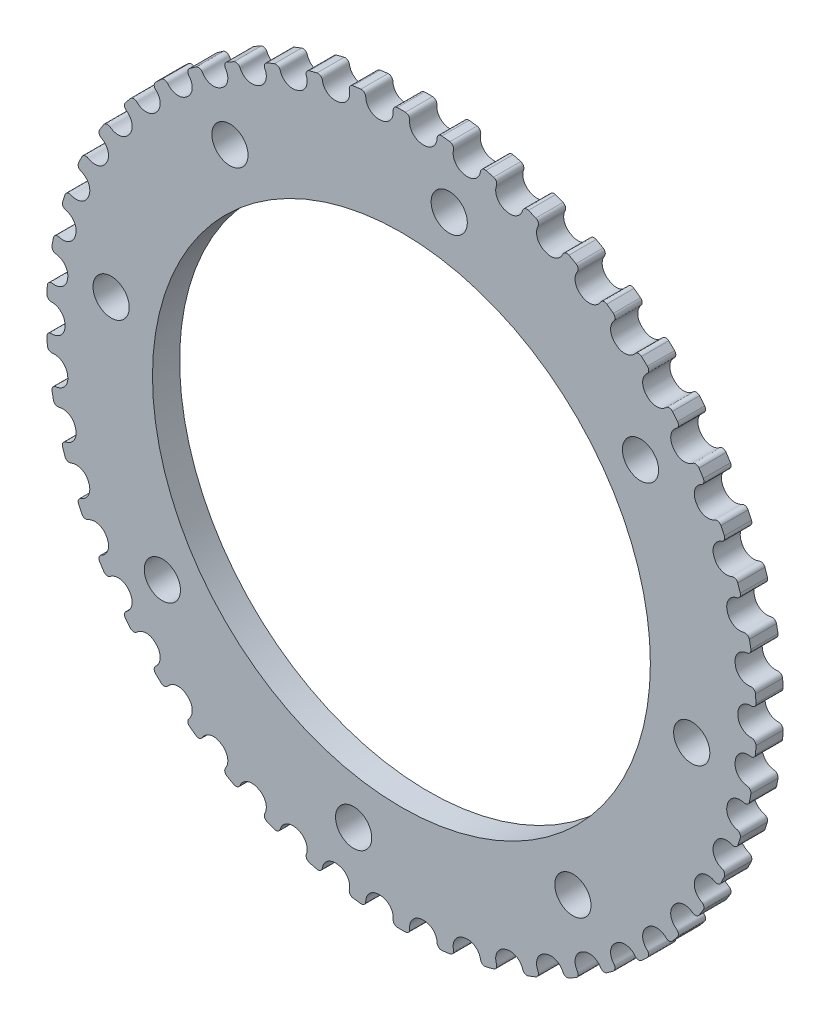
SolidWorks part; units mm, degrees
material "Thornel Mat VMA"
ref_plane "Front Plane" through (0, 0, 0) normal (0, 0, 1) x (1, 0, 0)
ref_plane "Top Plane" through (0, 0, 0) normal (0, 1, 0) x (1, 0, 0)
ref_plane "Right Plane" through (0, 0, 0) normal (1, 0, 0) x (0, 0, -1)
ref_axis "Axis1" through (0, 0, 55) along (0, 0, -1)
sketch "SketchRevolveGearBelt01" plane through (0, 0, 0) normal (1, 0, 0) x (0, 0, -1)
  line L0 (0, 0) -> (1, 0) construction
  line L1 (1.5, 0) -> (1.5, 39.2172)
  line L2 (1.5, 39.2172) -> (-1.5, 39.2172)
  line L3 (-1.5, 39.2172) -> (-1.5, 0)
  line L4 (-1.5, 0) -> (1.5, 0)
  dimension "GearBeltSide1" = 1.5
  dimension "GearBeltOutsideDiameter" = 39.2172
  dimension "GearBeltSide2" = 1.5
revolve "GearBelt01" add sketch "SketchRevolveGearBelt01" angle 360 about L0
sketch "SketchToothGearBelt01" plane through (0, 0, 0) normal (0, 0, 1) x (1, 0, 0)
  arc A0 (39.1647, 2.0323) -> (39.1647, -2.0323) centre (0, 0) cw
  spline S0 degree 3 poles (39.1647, -2.0323) (39.166, -2.006) (39.1649, -1.9663) (39.1569, -1.9141) (39.1478, -1.8755) (39.1356, -1.8378) (39.1204, -1.8013) (39.1023, -1.7661) (39.0814, -1.7324) (39.0578, -1.7006) (39.0317, -1.6708) (39.0033, -1.6432) (38.9728, -1.618) (38.9403, -1.5953) (38.9061, -1.5754) (38.8703, -1.5582) (38.8333, -1.5441) (38.7953, -1.533) (38.7565, -1.525) (38.7172, -1.5201) (38.6658, -1.5185) (38.59, -1.5198) (38.4897, -1.516) (38.3775, -1.5026) (38.2667, -1.4805) (38.158, -1.4498) (38.052, -1.4107) (37.9494, -1.3633) (37.8509, -1.3081) (37.7569, -1.2453) (37.6682, -1.1753) (37.5853, -1.0986) (37.5086, -1.0156) (37.4387, -0.9268) (37.376, -0.8329) (37.3208, -0.7343) (37.2735, -0.6317) (37.2344, -0.5257) (37.2037, -0.4169) (37.1817, -0.3061) (37.1683, -0.1939) (37.1652, -0.1051) (37.1655, -0.0405) (37.1655, 0) (37.1655, 0.0405) (37.1652, 0.1051) (37.1683, 0.1939) (37.1817, 0.3061) (37.2037, 0.4169) (37.2344, 0.5257) (37.2735, 0.6317) (37.3208, 0.7343) (37.376, 0.8329) (37.4387, 0.9268) (37.5086, 1.0156) (37.5853, 1.0986) (37.6682, 1.1753) (37.7569, 1.2453) (37.8509, 1.3081) (37.9494, 1.3633) (38.052, 1.4107) (38.158, 1.4498) (38.2667, 1.4805) (38.3775, 1.5026) (38.4897, 1.516) (38.59, 1.5198) (38.6658, 1.5185) (38.7172, 1.5201) (38.7565, 1.525) (38.7953, 1.533) (38.8333, 1.5441) (38.8703, 1.5582) (38.9061, 1.5754) (38.9403, 1.5953) (38.9728, 1.618) (39.0033, 1.6432) (39.0317, 1.6708) (39.0578, 1.7006) (39.0814, 1.7324) (39.1023, 1.7661) (39.1204, 1.8013) (39.1356, 1.8378) (39.1478, 1.8755) (39.1569, 1.9141) (39.1649, 1.9663) (39.166, 2.006) (39.1647, 2.0323) knots 0 0 0 0 0.012346 0.01852 0.024693 0.030866 0.037039 0.043212 0.049386 0.055559 0.061732 0.067905 0.074078 0.080252 0.086425 0.092598 0.098771 0.104944 0.111118 0.117291 0.123464 0.135171 0.152781 0.17039 0.188 0.205609 0.223219 0.240828 0.258438 0.276048 0.293657 0.311267 0.328876 0.346486 0.364095 0.381705 0.399315 0.416924 0.434534 0.452143 0.469753 0.487362 0.493681 0.5 0.506319 0.512638 0.530247 0.547857 0.565466 0.583076 0.600685 0.618295 0.635905 0.653514 0.671124 0.688733 0.706343 0.723952 0.741562 0.759172 0.776781 0.794391 0.812 0.82961 0.847219 0.864829 0.876536 0.882709 0.888882 0.895056 0.901229 0.907402 0.913575 0.919748 0.925922 0.932095 0.938268 0.944441 0.950614 0.956788 0.962961 0.969134 0.975307 0.98148 0.987654 1 1 1 1
extrude "ToothExtrudeCutGearBelt01" cut sketch "SketchToothGearBelt01" against normal blind 7.239 and the other way blind 7.239
pattern_circular "PatternGearBelt01" count 50 every 7.2 about axis through (0, 0, 55) along (0, 0, -1) of "ToothExtrudeCutGearBelt01"
sketch "BoreRevolveSketch" plane through (0, 0, 0) normal (1, 0, 0) x (0, 0, -1)
  line L0 (0, 0) -> (1, 0) construction
  line L1 (-7.239, 0) -> (7.239, 0)
  line L2 (7.239, 0) -> (7.239, 27.5)
  line L3 (7.239, 27.5) -> (-7.239, 27.5)
  line L4 (-7.239, 27.5) -> (-7.239, 0)
  dimension "BoreSide1" = 7.239
  dimension "TaperSide1" = 27.5
  dimension "BoreSide2" = 7.239
  dimension "TaperSide2" = 27.5
revolve "BoreRevolveCut" cut sketch "BoreRevolveSketch" angle 360 about L0
sketch "AuxiliarySketchGearBelt01" plane through (0, 0, 0) normal (0, 0, 1) x (1, 0, 0)
  circle A0 centre (0, 0) radius 39.7887 construction
  dimension "PitchDiameter" = 79.5774
sketch "Sketch1" plane through (0, 0, 1.5) normal (0, 0, 1) x (1, 0, 0)
  circle A0 centre (-26.4084, -18.9432) radius 2 construction
  circle A1 centre (-5.2787, -32.0684) radius 2 construction
  circle A2 centre (18.9432, -26.4084) radius 2 construction
  circle A3 centre (32.0684, -5.2787) radius 2 construction
  circle A4 centre (26.4084, 18.9432) radius 2 construction
  circle A5 centre (5.2787, 32.0684) radius 2 construction
  circle A6 centre (-18.9432, 26.4084) radius 2 construction
  circle A7 centre (-32.0684, 5.2787) radius 2 construction
  circle A8 centre (-26.4084, -18.9432) radius 2
  circle A9 centre (-5.2787, -32.0684) radius 2
  circle A10 centre (18.9432, -26.4084) radius 2
  circle A11 centre (32.0684, -5.2787) radius 2
  circle A12 centre (26.4084, 18.9432) radius 2
  circle A13 centre (5.2787, 32.0684) radius 2
  circle A14 centre (-18.9432, 26.4084) radius 2
  circle A15 centre (-32.0684, 5.2787) radius 2
extrude "Cut-Extrude1" cut sketch "Sketch1" against normal blind 10
